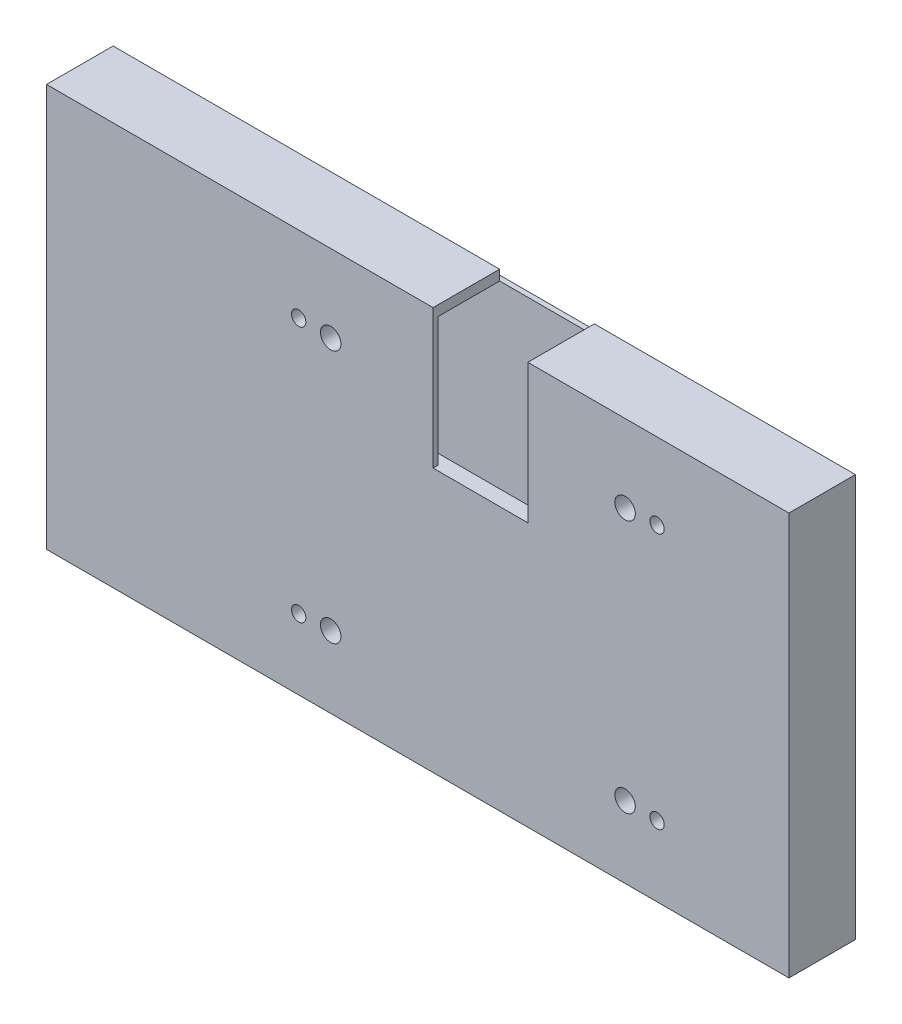
SolidWorks part; units mm, degrees
ref_plane "前视基准面" through (0, 0, 0) normal (0, 0, 1) x (1, 0, 0)
ref_plane "上视基准面" through (0, 0, 0) normal (0, 1, 0) x (1, 0, 0)
ref_plane "右视基准面" through (0, 0, 0) normal (1, 0, 0) x (0, 0, -1)
sketch "草图1" plane through (0, 0, 0) normal (0, 0, 1) x (1, 0, 0)
  line L0 (0, 24.75) -> (0, -24.75) construction
  line L1 (-28.75, -24.75) -> (28.75, -24.75) construction
  line L2 (-28.75, -24.75) -> (-28.75, 24.75) construction
  line L3 (-28.75, 24.75) -> (28.75, 24.75) construction
  line L4 (28.75, -24.75) -> (28.75, 24.75) construction
  line L5 (-28.75, -24.75) -> (28.75, 24.75) construction
  line L6 (-28.75, 24.75) -> (28.75, -24.75) construction
  line L7 (-28.75, 0) -> (28.75, 0) construction
  line L8 (-84.25, 39.9) -> (60.75, 39.9)
  line L9 (-78.75, 37.9) -> (55.25, 37.9)
  line L10 (-82.25, 34.4) -> (-82.25, -33.25)
  line L11 (-78.75, -36.75) -> (55.25, -36.75)
  line L12 (58.75, 34.4) -> (58.75, -33.25)
  line L13 (60.75, 39.9) -> (60.75, -38.75)
  line L14 (-84.25, -38.75) -> (60.75, -38.75)
  line L15 (-84.25, 39.9) -> (-84.25, -38.75)
  line L16 (0, 12.75) -> (0, 39.9) construction
  line L17 (-25.75, 39.9) -> (25.75, 39.9)
  line L18 (-25.75, 39.9) -> (-25.75, 12.75)
  line L19 (-25.75, 12.75) -> (25.75, 12.75)
  line L20 (25.75, 39.9) -> (25.75, 12.75)
  line L21 (-84.25, -12.25) -> (-63.6601, -12.25)
  line L22 (-84.25, -12.25) -> (-84.25, -27.25)
  line L23 (-84.25, -27.25) -> (-63.6601, -27.25)
  line L24 (-63.6601, -12.25) -> (-63.6601, -27.25)
  line L25 (58.75, 37.9) -> (58.75, -36.75) construction
  line L26 (-8.75, 39.9) -> (9.75, 39.9)
  line L27 (-8.75, 39.9) -> (-8.75, 12.75)
  line L28 (-8.75, 12.75) -> (9.75, 12.75)
  line L29 (9.75, 39.9) -> (9.75, 12.75)
  line L30 (-82.25, 37.9) -> (58.75, 37.9) construction
  line L31 (-82.25, -36.75) -> (58.75, -36.75) construction
  line L32 (-82.25, 37.9) -> (-82.25, -36.75) construction
  circle A0 centre (-28.75, 24.75) radius 2
  circle A1 centre (28.75, 24.75) radius 2
  circle A2 centre (28.75, -24.75) radius 2
  circle A3 centre (-28.75, -24.75) radius 2
  circle A4 centre (-35, 25) radius 1.4
  circle A5 centre (35, 25) radius 1.4
  circle A6 centre (35, -25) radius 1.4
  circle A7 centre (-35, -25) radius 1.4
  arc A8 (58.75, 34.4) -> (55.25, 37.9) centre (55.25, 34.4) ccw
  arc A9 (58.75, -33.25) -> (55.25, -36.75) centre (55.25, -33.25) cw
  arc A10 (-78.75, -36.75) -> (-82.25, -33.25) centre (-78.75, -33.25) cw
  arc A11 (-82.25, 34.4) -> (-78.75, 37.9) centre (-78.75, 34.4) cw
  point P0 (0, 0)
  dimension "D3" = 4
  dimension "D11" = 2.8
  dimension "D13" = 25
  dimension "D18" = 3.5
  dimension "D21" = 50
  dimension "D22" = 70
  dimension "D1" = 57.5
  dimension "D4" = 12
  dimension "D5" = 30
  dimension "D6" = 13.15
  dimension "D7" = 53.5
  dimension "D9" = 15
  dimension "D10" = 9.5
  dimension "D12" = 35
  dimension "D14" = 3
  dimension "D15" = 12
  dimension "D16" = 17
  dimension "D17" = 16
  dimension "D19" = 18.5
  dimension "D20" = 63.75
  dimension "D8" = 2
extrude "凸台-拉伸2" add sketch "草图1" against normal blind 3 contours L12 L9 L10 L11 A1 A0 A2 A3 region at (-11.6408, -2.3965, 0)
extrude "凸台-拉伸3" add sketch "草图1<3>" against normal blind 13 contours L8 L15 L14 L13 L9 L12 L11 L10 | L15 L21 L10 L9 L18 L8 | L27 L8 L18 L9 | L8 L29 L9 L20 region at (-55, 39.1163, 0) region at (-17.25, 38.9, 0) region at (-83.25, -28.8996, 0) region at (17.75, 38.9, 0)
sketch "草图1<3>" plane through (0, 0, 0) normal (0, 0, 1) x (1, 0, 0) same geometry as "草图1"
extrude "凸台-拉伸4" add sketch "草图1<4>" against normal blind 1 from surface contours L24 L21 L10 L23 | L15 L23 L10 L21 | L27 L9 L18 L19 | L27 L8 L18 L9 | L9 L29 L19 L20 | L8 L29 L9 L20 region at (-17.25, 38.9, 0) region at (-83.25, -19.75, 0) region at (-17.25, 25.325, 0) region at (-72.955, -19.75, 0) region at (17.75, 38.9, 0) region at (17.75, 25.325, 0) starting at face at (-21.3013, 11.2625, 0)
sketch "草图1<4>" plane through (0, 0, 0) normal (0, 0, 1) x (1, 0, 0) same geometry as "草图1"
extrude "凸台-拉伸6" add sketch "草图1<6>" against normal blind 1 from surface separate body contours L12 A9 L11 A10 L10 A11 L9 A8 starting at face at (-3.2327, -6.3635, -13)
sketch "草图1<6>" plane through (0, 0, 0) normal (0, 0, 1) x (1, 0, 0) same geometry as "草图1"
